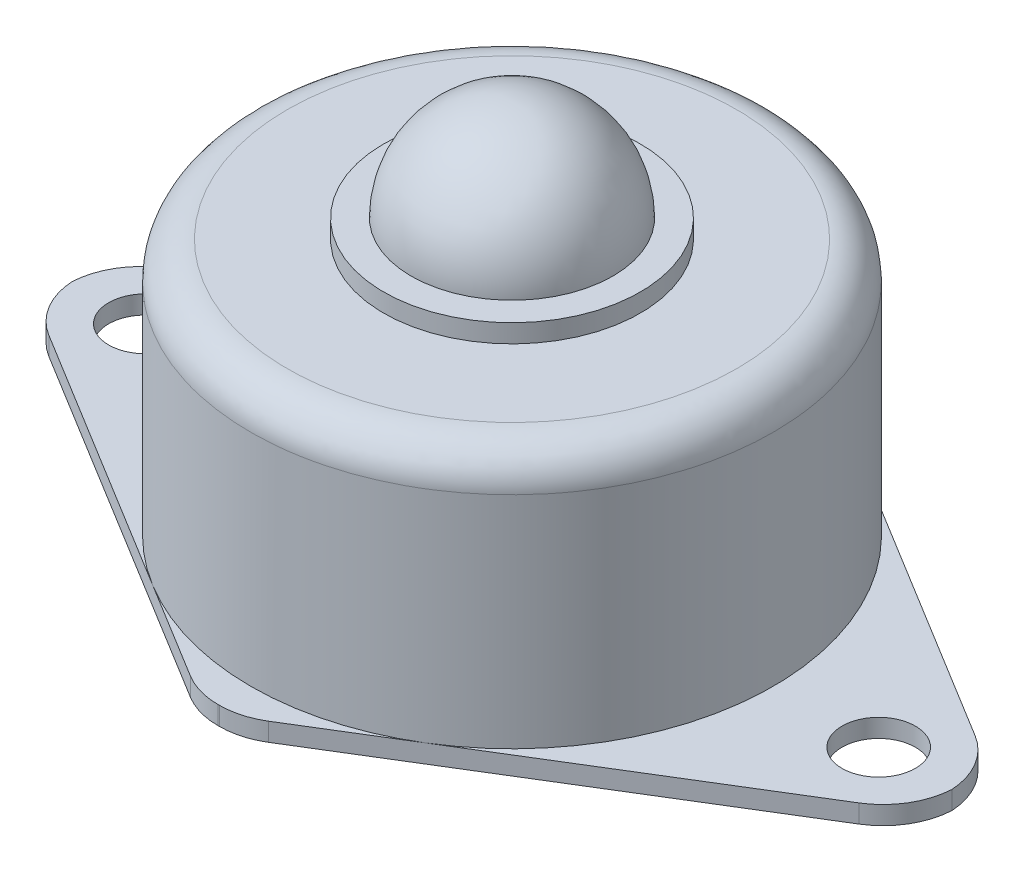
SolidWorks part; units mm, degrees
ref_plane "정면" through (0, 0, 0) normal (0, 0, 1) x (1, 0, 0)
ref_plane "윗면" through (0, 0, 0) normal (0, 1, 0) x (1, 0, 0)
ref_plane "우측면" through (0, 0, 0) normal (1, 0, 0) x (0, 0, -1)
sketch "스케치1" plane through (0, 0, 0) normal (0, 0, 1) x (1, 0, 0)
  line L0 (0, 20.5) -> (0, 0) construction
  line L1 (14.25, 20.5) -> (-14.25, 20.5) construction
  line L2 (14.25, 20.5) -> (14.25, 0) construction
  line L3 (14.25, 0) -> (-14.25, 0) construction
  line L4 (-14.25, 20.5) -> (-14.25, 0) construction
  line L5 (14.25, 20.5) -> (-14.25, 0) construction
  line L6 (14.25, 0) -> (-14.25, 20.5) construction
  line L7 (-14.25, 15) -> (14.25, 15) construction
  line L8 (-5.5, 15) -> (-7, 15)
  line L9 (-7, 15) -> (-7, 14)
  line L10 (-7, 14) -> (-14.25, 14)
  line L11 (-14.25, 14) -> (-14.25, 0)
  line L12 (-14.25, 0) -> (0, 0)
  line L13 (0, 20.5) -> (0, 0)
  arc A0 (-5.5, 15) -> (0, 20.5) centre (0, 15) cw
  point P0 (0, 10.25)
  point P8 (0, 0)
  dimension "D1" = 28.5
  dimension "D2" = 20.5
  dimension "D3" = 15
  dimension "D4" = 1
  dimension "D5" = 1.5
revolve "회전1" add sketch "스케치1" angle 360 about L0
fillet "필렛1" radius 2 1 edges at (-14.25, 14, 0) first distance on face at (-14.25, 0, 0)
sketch "스케치2" plane through (0, 0, 0) normal (0, 1, 0) x (1, 0, 0)
  line L0 (0, 16) -> (0, -16) construction
  line L1 (-24, 0) -> (24, 0) construction
  line L6 (-24, 2) -> (-1.1666, 16)
  line L7 (24, 16) -> (-24, 16)
  line L8 (24, 16) -> (24, -16)
  line L9 (24, -16) -> (-24, -16)
  line L10 (-24, 16) -> (-24, -16)
  line L11 (24, 16) -> (-24, -16) construction
  line L12 (24, -16) -> (-24, 16) construction
  line L13 (24, 2) -> (1.1666, 16)
  line L14 (24, -2) -> (1.1666, -16)
  line L15 (-24, -2) -> (-1.1666, -16)
  circle A0 centre (-20, 0) radius 2
  circle A1 centre (20, 0) radius 2
  circle A2 centre (0, 0) radius 14.25 construction
  point P9 (0, 0)
  point P18 (-1.3566, 16)
  dimension "D4" = 4
  dimension "D1" = 48
  dimension "D2" = 32
  dimension "D3" = 40
  dimension "D5" = 2
extrude "보스-돌출1" add sketch "스케치2" against normal blind 1 contours L10 L15 L9 L14 L8 L13 L7 L6 A0 A1 region at (0, 0, 0)
fillet "필렛2" radius 4 8 edges at (24, -0.5, -2) (24, -0.5, 2) (1.1666, -0.5, 16) (-1.1666, -0.5, 16) (-24, -0.5, 2) (-24, -0.5, -2) (1.1666, -0.5, -16) (-1.1666, -0.5, -16)
